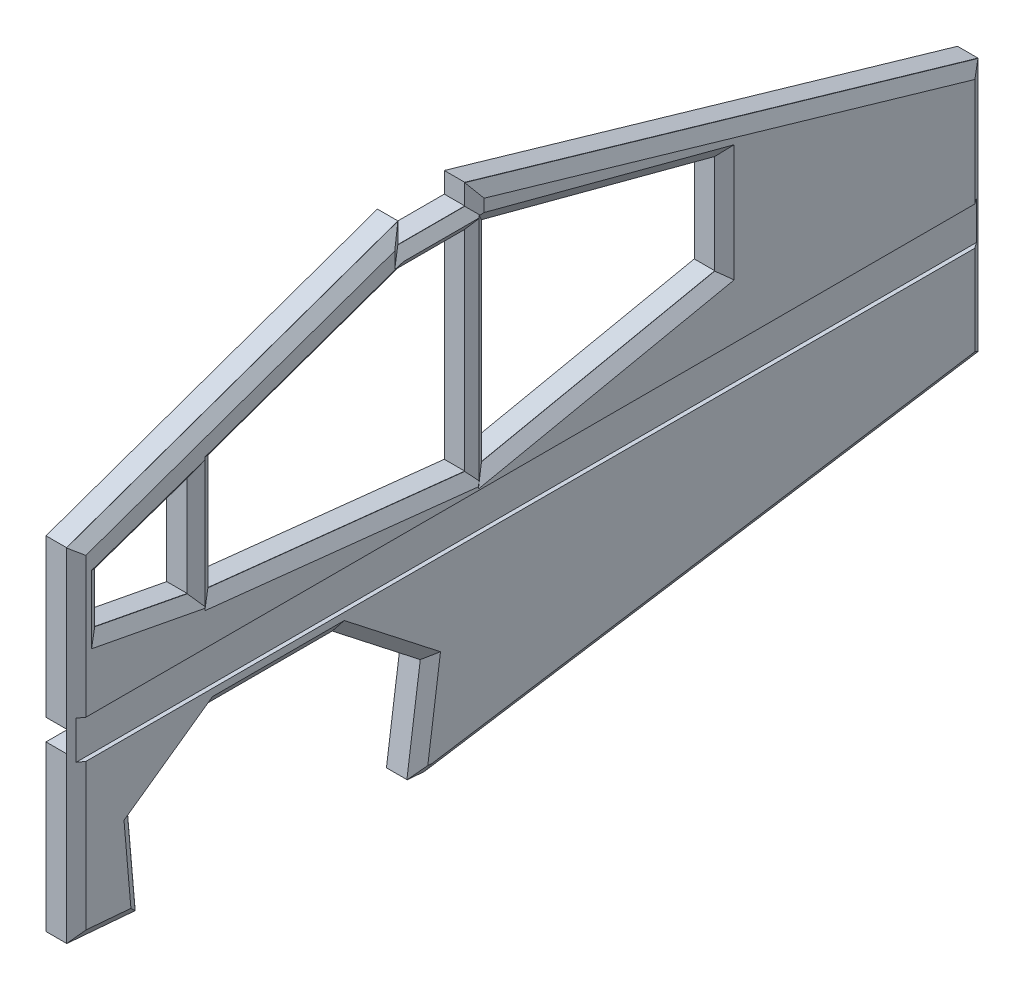
SolidWorks part; units mm, degrees
ref_plane "Front Plane" through (0, 0, 0) normal (0, 0, 1) x (1, 0, 0)
ref_plane "Top Plane" through (0, 0, 0) normal (0, 1, 0) x (1, 0, 0)
ref_plane "Right Plane" through (0, 0, 0) normal (1, 0, 0) x (0, 0, -1)
sketch "Sketch1" plane through (0, 0, 0) normal (1, 0, 0) x (0, 0, -1)
  line L7 (0, 117.5774) -> (159.1764, 117.5774) construction
  line L8 (159.1764, -7.4049) -> (159.1764, 71.351)
  line L9 (-123.5256, 81.219) -> (-123.5256, 117.5774) construction
  line L11 (-123.5256, 117.5774) -> (-31.374, 117.5774) construction
  line L12 (159.1764, 71.351) -> (159.1764, 117.5774) construction
  line L22 (-123.5256, 81.219) -> (-123.5256, -25.0829)
  line L51 (5.2018, 40.001) -> (77.5282, 55.0563)
  line L52 (77.5282, 55.0563) -> (77.5282, 85.8304)
  line L54 (-12.5619, -34.3386) -> (159.1764, -7.4049)
  line L55 (-123.5256, -25.0829) -> (-102.221, -26.86)
  line L56 (-102.221, -26.86) -> (-104.557, 0)
  line L57 (-104.557, 0) -> (-79.6468, 17.6863)
  line L58 (-79.6468, 17.6863) -> (-41.0945, 17.6863)
  line L59 (-41.0945, 17.6863) -> (-13.7798, -3.6413)
  line L60 (-13.7798, -3.6413) -> (-17.9475, -33.8894)
  line L61 (-17.9475, -33.8894) -> (-12.5619, -34.3386)
  line L67 (-79.6468, 84.2241) -> (-79.6468, 48.574)
  line L76 (-79.6468, 84.2241) -> (-20.7359, 105.0152)
  line L77 (-20.7359, 105.0152) -> (0, 105.0152)
  line L78 (0, 105.0152) -> (0, 40.0073)
  line L79 (5.2018, 40.001) -> (5.2018, 105.0152)
  line L80 (5.2018, 105.0152) -> (77.5282, 85.8304)
  line L81 (0, 40.0073) -> (-79.6468, 48.574)
  line L82 (-86.0905, 81.219) -> (-86.0905, 50.1978)
  line L85 (-86.0905, 81.219) -> (-114.76, 71.351)
  line L87 (-114.76, 71.351) -> (-114.76, 55.6667)
  line L88 (-114.76, 55.6667) -> (-86.0905, 50.1978)
  line L89 (-123.5256, 81.219) -> (-20.7359, 117.5774)
  line L91 (0, 117.5774) -> (159.1764, 71.351)
  line L92 (-20.7359, 117.5774) -> (-20.7359, 111.2274)
  line L93 (-20.7359, 111.2274) -> (0, 111.2274)
  line L94 (0, 111.2274) -> (0, 117.5774)
  dimension "D1" = 282.702
  dimension "D2" = 6.35
extrude "Boss-Extrude1" add sketch "Sketch1" along normal blind 6.35
sketch "Sketch2" plane through (6.35, 0, 0) normal (1, 0, 0) x (0, 0, -1)
  line L33 (-123.5256, 81.219) -> (-123.5256, -25.0829) construction
  line L38 (159.1764, -7.4049) -> (159.1764, 71.351) construction
  line L39 (159.1764, 25.8619) -> (76.5252, 25.8619)
  line L40 (159.1764, 25.8619) -> (159.1764, 32.3891)
  line L41 (159.1764, 32.3891) -> (76.5252, 32.3891)
  line L42 (76.5252, 25.8619) -> (76.5252, 32.3891)
  line L44 (-123.5256, 32.4659) -> (-123.5256, 25.8619)
  line L46 (-46.5558, 32.4659) -> (-46.5558, 25.8619)
  line L47 (-123.5256, 32.4659) -> (-46.5558, 32.4659)
  line L48 (-46.5558, 25.8619) -> (-123.5256, 25.8619)
  dimension "D3" = 6.5272
  dimension "D4" = 6.604
extrude "Cut-Extrude1" cut sketch "Sketch2" against normal through all
sketch "Sketch4" plane through (6.35, 0, 0) normal (1, 0, 0) x (0, 0, -1)
  line L1 (-123.5256, 81.2474) -> (-123.5256, -26.2693) construction
  line L2 (-123.5256, 35.1881) -> (158.7607, 35.1881)
  line L3 (-123.5256, 35.1881) -> (-123.5256, 23.3267)
  line L4 (-123.5256, 23.3267) -> (158.7607, 23.3267)
  line L5 (158.7607, 35.1881) -> (158.7607, 23.3267)
sketch "Sketch5" plane through (6.35, 0, 0) normal (1, 0, 0) x (0, 0, -1)
  line L2 (-0.017, 117.4897) -> (159.1594, 117.4897) construction
  line L4 (159.1594, -7.4926) -> (159.1594, 71.2633)
  line L5 (-123.5426, 81.1313) -> (-123.5426, 117.4897) construction
  line L6 (-123.5426, 117.4897) -> (-31.391, 117.4897) construction
  line L9 (159.1594, 71.2633) -> (159.1594, 117.4897) construction
  line L10 (-123.5426, 81.1313) -> (-123.5426, -25.1706)
  line L11 (5.1849, 39.9134) -> (77.5113, 54.9686)
  line L30 (77.5113, 54.9686) -> (77.5113, 85.7427)
  line L31 (-12.5789, -34.4263) -> (159.1594, -7.4926)
  line L32 (-123.5426, -25.1706) -> (-102.238, -26.9477)
  line L33 (-102.238, -26.9477) -> (-104.574, -0.0877)
  line L34 (-104.574, -0.0877) -> (-79.6638, 17.5986)
  line L35 (-79.6638, 17.5986) -> (-41.1115, 17.5986)
  line L36 (-41.1115, 17.5986) -> (-13.7968, -3.729)
  line L37 (-13.7968, -3.729) -> (-17.9645, -33.9771)
  line L38 (-17.9645, -33.9771) -> (-12.5789, -34.4263)
  line L39 (-79.6638, 84.1365) -> (-79.6638, 48.4864)
  line L40 (-79.6638, 84.1365) -> (-20.7529, 104.9275)
  line L41 (-20.7529, 104.9275) -> (-0.017, 104.9275)
  line L42 (-0.017, 104.9275) -> (-0.017, 39.9196)
  line L43 (5.1849, 39.9134) -> (5.1849, 104.9275)
  line L44 (5.1849, 104.9275) -> (77.5113, 85.7427)
  line L45 (-0.017, 39.9196) -> (-79.6638, 48.4864)
  line L46 (-86.1075, 81.1313) -> (-86.1075, 50.1101)
  line L47 (-86.1075, 81.1313) -> (-114.777, 71.2633)
  line L48 (-114.777, 71.2633) -> (-114.777, 55.579)
  line L49 (-114.777, 55.579) -> (-86.1075, 50.1101)
  line L50 (-123.5426, 81.1313) -> (-20.7529, 117.4897)
  line L51 (-0.017, 117.4897) -> (159.1594, 71.2633)
  line L52 (-20.7529, 117.4897) -> (-20.7529, 111.1397)
  line L53 (-20.7529, 111.1397) -> (-0.017, 111.1397)
  line L54 (-0.017, 111.1397) -> (-0.017, 117.4897)
  dimension "D1" = 6.35
extrude "Boss-Extrude2" add sketch "Sketch5" along normal blind 2.54 draft 54
extrude "Cut-Extrude2" cut sketch "Sketch4" along normal blind 2.54 from offset 1.27
